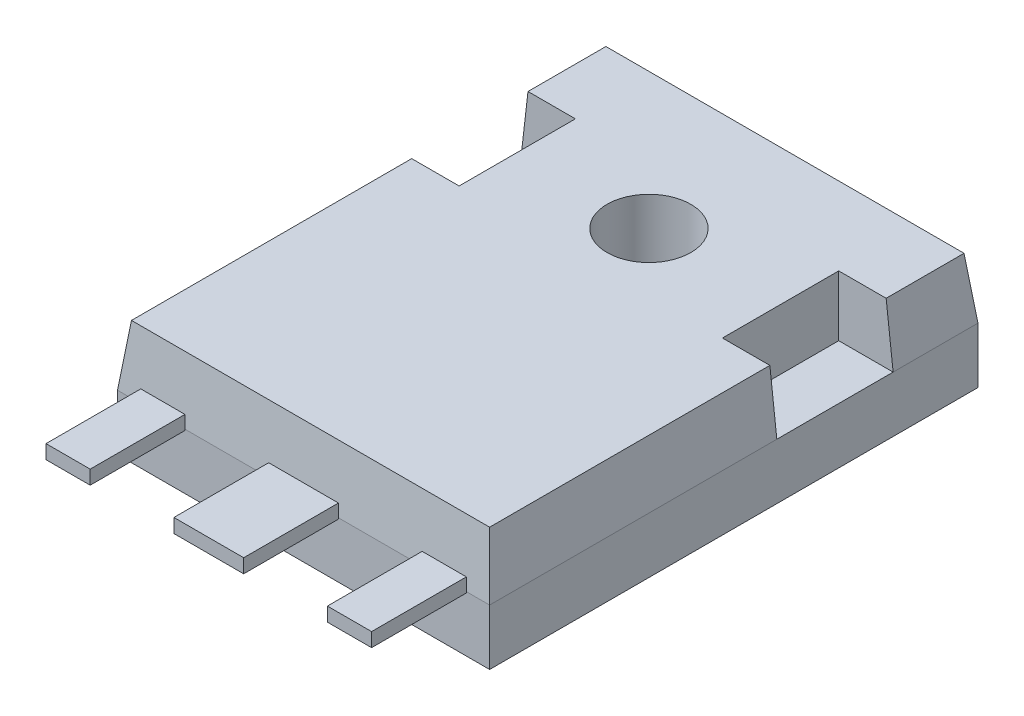
SolidWorks part; units mm, degrees
ref_plane "Front Plane" through (0, 0, 0) normal (0, 0, 1) x (1, 0, 0)
ref_plane "Top Plane" through (0, 0, 0) normal (0, 1, 0) x (1, 0, 0)
ref_plane "Right Plane" through (0, 0, 0) normal (1, 0, 0) x (0, 0, -1)
sketch "Sketch1" plane through (0, 0, 0) normal (0, 1, 0) x (1, 0, 0)
  line L1 (-8, -10.5) -> (8, -10.5)
  line L2 (-8, -10.5) -> (-8, 10.5)
  line L3 (-8, 10.5) -> (8, 10.5)
  line L4 (8, -10.5) -> (8, 10.5)
  line L5 (-8, -10.5) -> (8, 10.5) construction
  line L6 (-8, 10.5) -> (8, -10.5) construction
  point P0 (0, 0)
  dimension "D1" = 16
  dimension "D2" = 21
extrude "Boss-Extrude1" add sketch "Sketch1" along normal blind 5
sketch "Sketch2" plane through (0, 5, 0) normal (0, 1, 0) x (1, 0, 0)
  line L0 (-8, 10.5) -> (-8, -10.5) construction
  line L1 (-8, 6.85) -> (-5.6618, 6.85)
  line L2 (-8, 6.85) -> (-8, 1.85)
  line L3 (-8, 1.85) -> (-5.6618, 1.85)
  line L4 (-5.6618, 6.85) -> (-5.6618, 1.85)
  line L6 (0, 13.2908) -> (0, -15.2211) construction
  line L7 (8, 6.85) -> (8, 1.85)
  line L8 (8, 1.85) -> (5.6618, 1.85)
  line L9 (5.6618, 6.85) -> (5.6618, 1.85)
  line L10 (8, 6.85) -> (5.6618, 6.85)
  line L11 (-11.1878, 4.35) -> (9.4633, 4.35) construction
  line L12 (8, 10.5) -> (-8, 10.5) construction
  point P15 (-5.6618, 4.35)
  dimension "D1" = 6.15
  dimension "D2" = 5
extrude "Cut-Extrude1" cut sketch "Sketch2" against normal blind 2.6
sketch "Sketch3" plane through (0, 5, 0) normal (0, 1, 0) x (1, 0, 0)
  line L0 (0, 22.549) -> (0, -13.849) construction
  line L1 (-9.7226, 4.35) -> (9.7226, 4.35) construction
  line L2 (-5.6618, 1.85) -> (-5.6618, 6.85) construction
  line L3 (-5.6618, 6.85) -> (-5.6618, 1.85)
  circle A0 centre (0, 4.35) radius 1.8
  point P9 (-5.6618, 4.35)
  point P14 (0, 4.35)
  dimension "D1" = 3.6
extrude "Cut-Extrude2" cut sketch "Sketch3" against normal through all contours A0 region at (0, 5, -4.35)
chamfer "Chamfer1" distance 2.6 distance2 0.3 6 edges at (8, 5, 4.325) (-8, 5, 4.325) (8, 5, -8.675) (0, 5, -10.5) (-8, 5, -8.675) (0, 5, 10.5) first distance on face at (8, 3.1, -2.175) first distance on face at (-8, 3.1, -2.175) first distance on face at (0, 2.5, -10.5) first distance on face at (0, 2.5, 10.5)
sketch "Sketch4" plane through (0, 0, 10.5) normal (0, 0, 1) x (1, 0, 0)
  line L0 (-8, 0) -> (8, 0) construction
  line L1 (-7, 2.35) -> (-5.1, 2.35)
  line L2 (-7, 2.35) -> (-7, 2.95)
  line L3 (-7, 2.95) -> (-5.1, 2.95)
  line L4 (-5.1, 2.35) -> (-5.1, 2.95)
  line L5 (-8, 2.4) -> (-8, 0) construction
  line L6 (0, 8.4757) -> (0, -5.9854) construction
  line L7 (5.1, 2.35) -> (5.1, 2.95)
  line L8 (7, 2.35) -> (5.1, 2.35)
  line L9 (7, 2.35) -> (7, 2.95)
  line L10 (7, 2.95) -> (5.1, 2.95)
  line L11 (8, 2.4) -> (-8, 2.4) construction
  line L12 (-1.5, 2.35) -> (1.5, 2.35)
  line L13 (-1.5, 2.35) -> (-1.5, 2.95)
  line L14 (-1.5, 2.95) -> (1.5, 2.95)
  line L15 (1.5, 2.35) -> (1.5, 2.95)
  point P15 (0, 2.4)
  dimension "D1" = 1.9
  dimension "D2" = 0.6
  dimension "D3" = 2.35
  dimension "D4" = 1
  dimension "D5" = 3
  dimension "D6" = 0.6
extrude "Boss-Extrude2" add sketch "Sketch4" along normal blind 4.5
sketch "Sketch5" plane through (0, 0, 15) normal (0, 0, 1) x (1, 0, 0)
  line L0 (-7, 2.35) -> (-5.1, 2.35) construction
  line L1 (-6.65, 2.35) -> (-5.45, 2.35)
  line L2 (-6.65, 2.35) -> (-6.65, 2.95)
  line L3 (-6.65, 2.95) -> (-5.45, 2.95)
  line L4 (-5.45, 2.35) -> (-5.45, 2.95)
  line L5 (-5.1, 2.95) -> (-7, 2.95) construction
  line L6 (-1.5, 2.35) -> (1.5, 2.35) construction
  line L7 (-0.6, 2.35) -> (0.6, 2.35)
  line L8 (-0.6, 2.35) -> (-0.6, 2.95)
  line L9 (-0.6, 2.95) -> (0.6, 2.95)
  line L10 (0.6, 2.35) -> (0.6, 2.95)
  line L11 (1.5, 2.95) -> (-1.5, 2.95) construction
  line L12 (0, 6.777) -> (0, -3.7589) construction
  line L13 (5.45, 2.35) -> (5.45, 2.95)
  line L14 (6.65, 2.95) -> (5.45, 2.95)
  line L15 (6.65, 2.35) -> (6.65, 2.95)
  line L16 (6.65, 2.35) -> (5.45, 2.35)
  point P20 (-6.05, 2.95)
  point P21 (0, 2.95)
  dimension "D1" = 1.2
  dimension "D2" = 1.2
extrude "Boss-Extrude3" add sketch "Sketch5" along normal blind 15.5
chamfer "Chamfer2" distance 0.4 angle 45 4 edges
chamfer "Chamfer3" distance 1 angle 45 2 edges
chamfer "Chamfer4" distance 0.5 angle 45 6 edges at (5.45, 2.65, 30.5) (6.65, 2.65, 30.5) (0.6, 2.65, 30.5) (-0.6, 2.65, 30.5) (-5.45, 2.65, 30.5) (-6.65, 2.65, 30.5)
sketch "Sketch6" plane through (0, 2.95, 0) normal (0, 1, 0) x (1, 0, 0)
  line L0 (8, -10.5) -> (7, -10.5) construction
  line L1 (-10.394, -17.755) -> (10.7254, -17.755)
  line L2 (-10.394, -17.755) -> (-10.394, -30.9402)
  line L3 (-10.394, -30.9402) -> (10.7254, -30.9402)
  line L4 (10.7254, -17.755) -> (10.7254, -30.9402)
  dimension "D1" = 7.255
  dimension "D2" = 21.1194
extrude "Cut-Extrude3" cut sketch "Sketch6" against normal through all
other "Flex1" [suppressed] parameters "D0"=139.19, "D1"=25.6194, "D2"=0
sketch "Sketch7" plane through (0, 2.95, 0) normal (0, 1, 0) x (1, 0, 0)
  line L0 (-1010.7966, -14.075) -> (48989.2034, -14.075) construction
  line L1 (-1020.307, -14.575) -> (48979.693, -14.575) construction
  line L3 (-8, -14.575) -> (7.716, -14.575)
  line L4 (-8, -14.575) -> (-8, -18.2514)
  line L5 (-8, -18.2514) -> (7.716, -18.2514)
  line L6 (7.716, -14.575) -> (7.716, -18.2514)
  point P6 (-8, -10.5)
  dimension "D1" = 3.575
  dimension "D2" = 0.5
extrude "Cut-Extrude4" cut sketch "Sketch7" against normal through all
